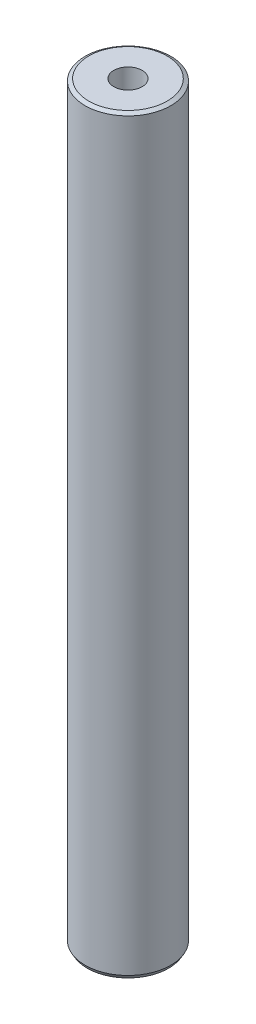
SolidWorks part; units mm, degrees
ref_plane "Front Plane" through (0, 0, 0) normal (0, 0, 1) x (1, 0, 0)
ref_plane "Top Plane" through (0, 0, 0) normal (0, 1, 0) x (1, 0, 0)
ref_plane "Right Plane" through (0, 0, 0) normal (1, 0, 0) x (0, 0, -1)
sketch "Sketch1" plane through (0, 0, 0) normal (0, 1, 0) x (1, 0, 0)
  circle A0 centre (0, 0) radius 32.5
  dimension "SHAFT_OD" = 65
extrude "Boss-Extrude1" add sketch "Sketch1" along normal blind 569.1319
sketch "Sketch2" plane through (0, 0, 0) normal (0, 1, 0) x (1, 0, 0)
  circle A0 centre (0, 0) radius 10.7628
  dimension "BORE_D" = 21.5256
extrude "Cut-Extrude1" cut sketch "Sketch2" along normal through all
chamfer "Chamfer1" distance 1.6112 angle 60 2 edges at (0, 569.1319, 32.5) (0, 0, 32.5) first distance on face at (0, 569.1319, 32.5) first distance on face at (0, 0, 10.7628)
